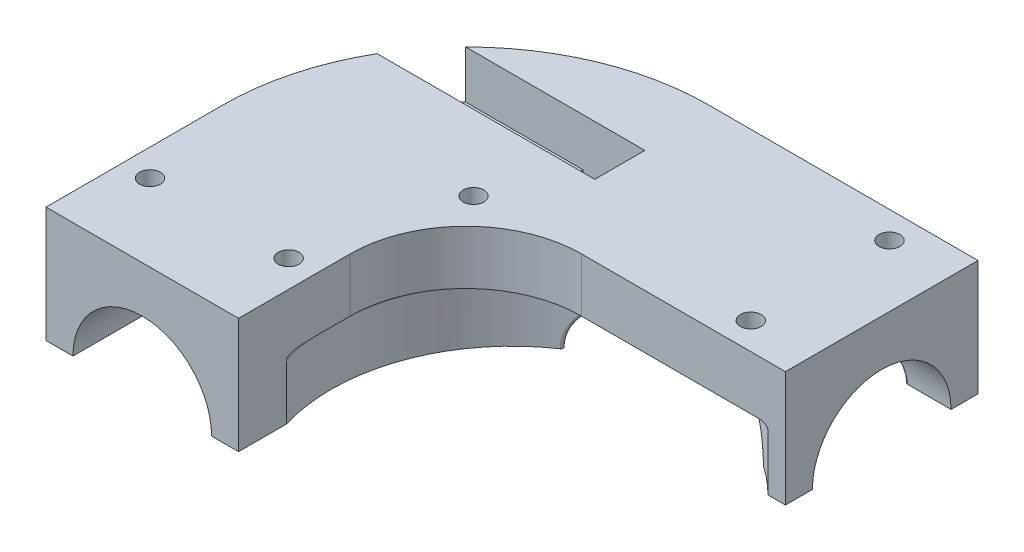
SolidWorks part; units mm, degrees
material "PLA"
ref_plane "前视基准面" through (0, 0, 0) normal (0, 0, 1) x (1, 0, 0)
ref_plane "上视基准面" through (0, 0, 0) normal (0, 1, 0) x (1, 0, 0)
ref_plane "右视基准面" through (0, 0, 0) normal (1, 0, 0) x (0, 0, -1)
sketch "草图1" plane through (0, 0, 0) normal (0, 1, 0) x (1, 0, 0)
  line L0 (0, 0) -> (-34.9545, 0) construction
  line L1 (-54, -19.0455) -> (-54, -42) construction
  line L2 (-66.5, -42) -> (-66.5, -19.0455)
  line L3 (-34.9545, 12.5) -> (0, 12.5)
  line L4 (0, 12.5) -> (0, -12.5)
  line L5 (0, -12.5) -> (-26.5, -12.5)
  line L6 (-41.5, -27.5) -> (-41.5, -42)
  line L7 (-41.5, -42) -> (-66.5, -42)
  arc A0 (-34.9545, 0) -> (-54, -19.0455) centre (-34.9545, -19.0455) ccw construction
  circle A1 centre (-19, -29) radius 22.5 construction
  arc A2 (-66.5, -19.0455) -> (-34.9545, 12.5) centre (-34.9545, -19.0455) cw
  arc A3 (-26.5, -12.5) -> (-41.5, -27.5) centre (-26.5, -27.5) ccw
  circle A4 centre (-29.9545, 0) radius 8.5 construction
  point P17 (-54, -42)
  point P20 (0, 0)
  dimension "D1" = 45
  dimension "D3" = 19
  dimension "D7" = 15
  dimension "D8" = 17
  dimension "D2" = 29
  dimension "D4" = 35
  dimension "D5" = 13
  dimension "D6" = 25
  dimension "D9" = 5
extrude "凸台-拉伸1" add sketch "草图1" along normal blind 15
sketch "草图2" plane through (0, 0, 42) normal (0, 0, 1) x (1, 0, 0)
  line L0 (-66.5, 0) -> (-41.5, 0) construction
  circle A0 centre (-54, 0) radius 9
  dimension "D1" = 18
sketch "草图3" plane through (0, 0, 0) normal (0, -1, 0) x (1, 0, 0)
  line L0 (-54, 42) -> (-54, 19.0455)
  line L1 (-45, 42) -> (-63, 42) construction
  line L2 (-34.9545, 0) -> (0, 0)
  arc A0 (-54, 19.0455) -> (-34.9545, 0) centre (-34.9545, 19.0455) ccw
  arc A1 (-66.5, 19.0455) -> (-34.9545, -12.5) centre (-34.9545, 19.0455) ccw construction
sweep "切除-扫描1" cut profiles "草图2" path "草图3"
sketch "草图4" plane through (0, 0, 0) normal (0, -1, 0) x (1, 0, 0)
  line L0 (-19, -29) -> (-19, 29) construction
  line L1 (-45, 42) -> (-63, 42) construction
  circle A0 centre (-19, 29) radius 23.5
  circle A1 centre (-19, -29) radius 23.5
  point P4 (-19, 0)
  point P9 (-54, 42)
  dimension "D2" = 47
  dimension "D1" = 58
  dimension "D3" = 35
extrude "切除-拉伸1" cut sketch "草图4" against normal blind 8
sketch "草图5" plane through (0, 15, 0) normal (0, 1, 0) x (1, 0, 0)
  line L0 (-66.5, -42) -> (-41.5, -42) construction
  line L1 (-66.5, 3.25) -> (-34, 3.25)
  line L2 (-66.5, 3.25) -> (-66.5, -3.25)
  line L3 (-66.5, -3.25) -> (-34, -3.25)
  line L4 (-34, 3.25) -> (-34, -3.25)
  line L5 (-66.5, -19.0455) -> (-66.5, -42) construction
  line L10 (-66.5, 0) -> (0, 0) construction
  point P4 (-34, 0)
  point P8 (-54, -42)
  dimension "D1" = 6.5
  dimension "D2" = 20
extrude "切除-拉伸2" cut sketch "草图5" against normal blind 6.2
fillet "圆角1" radius 0.8 2 edges at (-18.9934, 8, -5.5) (-30.9929, 8, 8.7906)
fillet "圆角2" radius 0.3 2 edges at (-18.3532, 7.117, -5.5089) (-19.6468, 7.117, 5.5089)
sketch "草图7" plane through (0, 15, 0) normal (0, 1, 0) x (1, 0, 0)
  line L0 (-54, -42) -> (-54, -19.0455) construction
  line L1 (-66.5, -42) -> (-41.5, -42) construction
  line L2 (0, 0) -> (-34.9545, 0) construction
  line L3 (-63, -32) -> (-45, -32) construction
  line L4 (-8, 9) -> (-8, -9) construction
  line L5 (0, -12.5) -> (0, 12.5) construction
  arc A0 (-34.9545, 0) -> (-54, -19.0455) centre (-34.9545, -19.0455) ccw construction
  arc A1 (-62.2605, -3.25) -> (-66.5, -19.0455) centre (-34.9545, -19.0455) ccw construction
  circle A2 centre (-45, -32) radius 1.35
  circle A3 centre (-63, -32) radius 1.35
  circle A4 centre (-8, -9) radius 1.35
  circle A5 centre (-8, 9) radius 1.35
  circle A6 centre (-40, -13) radius 1.35
  dimension "D3" = 2.7
  dimension "D6" = 13
  dimension "D7" = 40
  dimension "D1" = 10
  dimension "D2" = 18
  dimension "D4" = 8
  dimension "D5" = 18
extrude "切除-拉伸4" cut sketch "草图7" against normal blind 5
sketch "草图8" plane through (0, 8.8, 0) normal (0, 1, 0) x (1, 0, 0)
  line L0 (-62.2605, -3.25) -> (-34, -3.25) construction
  line L1 (-34, 3.25) -> (-42, 3.25)
  line L2 (-34, 3.25) -> (-34, -3.25)
  line L3 (-34, -3.25) -> (-42, -3.25)
  line L4 (-42, 3.25) -> (-42, -3.25)
  dimension "D1" = 8
extrude "切除-拉伸5" cut sketch "草图8" against normal up to next
